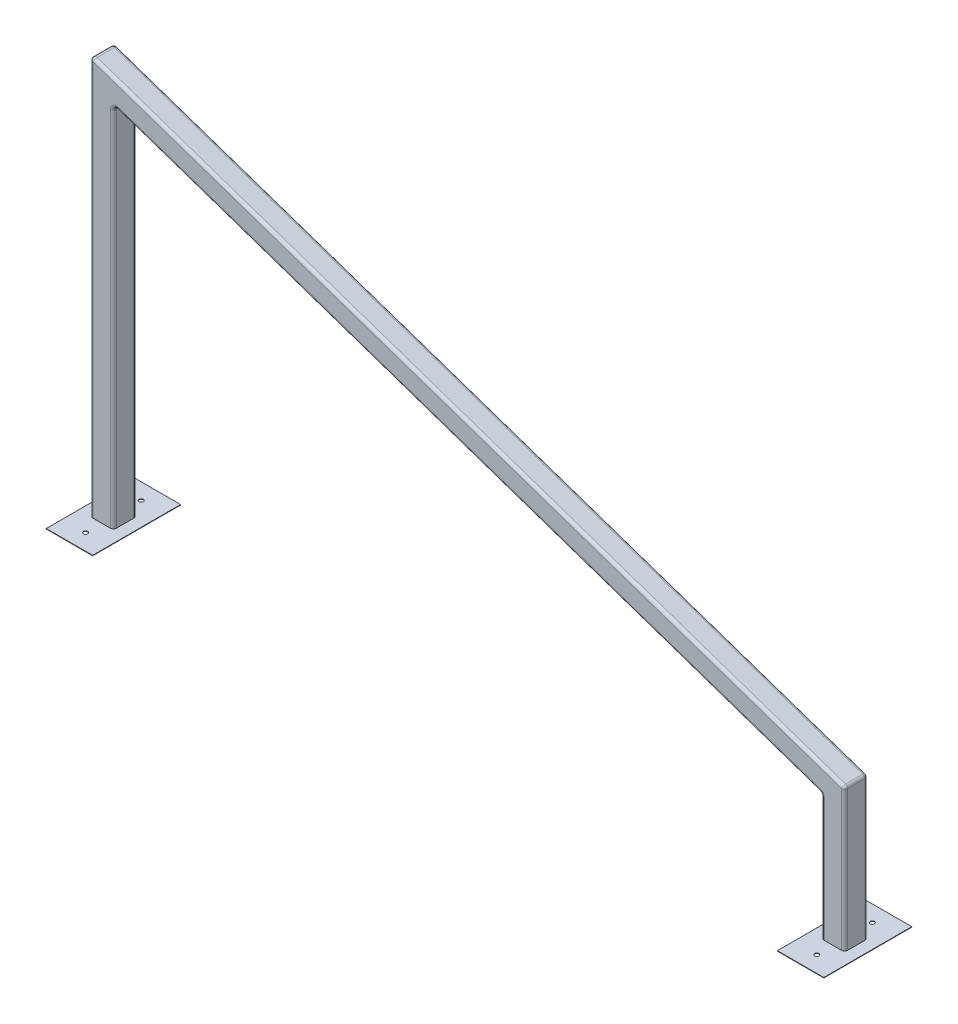
SolidWorks part; units mm, degrees
ref_plane "Alzado" through (0, 0, 0) normal (0, 0, 1) x (1, 0, 0)
ref_plane "Planta" through (0, 0, 0) normal (0, 1, 0) x (1, 0, 0)
ref_plane "Vista lateral" through (0, 0, 0) normal (1, 0, 0) x (0, 0, -1)
sketch "Croquis1" plane through (0, 0, 0) normal (0, 0, 1) x (1, 0, 0)
  line L0 (19.05, 0) -> (19.05, 600.7623)
  line L1 (19.05, 600.7623) -> (1178.0763, 205.7334)
  line L2 (1178.0763, 205.7334) -> (1178.0763, 0)
  line L3 (1178.0763, 0) -> (1216.1763, 0)
  line L4 (1216.1763, 0) -> (1216.1763, 233)
  line L5 (1216.1763, 233) -> (-19.05, 654)
  line L6 (-19.05, 654) -> (-19.05, 0)
  line L7 (-19.05, 0) -> (19.05, 0)
  point P6 (0, 0)
  point P10 (0, 0)
  dimension "D1" = 654
  dimension "D2" = 233
  dimension "D3" = 1305
  dimension "D4" = 38.1
  dimension "D5" = 38.1
extrude "Saliente-Extruir1" add sketch "Croquis1" along normal mid plane 38.1
sketch "Croquis3" plane through (0, 0, 0) normal (0, -1, 0) x (1, 0, 0)
  line L0 (1197.1263, 19.05) -> (1197.1263, 72) construction
  line L1 (38, -72) -> (-38, -72)
  line L2 (38, -72) -> (38, 72)
  line L3 (38, 72) -> (-38, 72)
  line L4 (-38, -72) -> (-38, 72)
  line L5 (38, -72) -> (-38, 72) construction
  line L6 (38, 72) -> (-38, -72) construction
  line L7 (1178.0763, 19.05) -> (1178.0763, -19.05) construction
  line L8 (1178.0763, 0) -> (1216.1763, 0) construction
  line L9 (1216.1763, 19.05) -> (1216.1763, -19.05) construction
  line L10 (0, 19.05) -> (0, 72) construction
  line L11 (1159.1263, -72) -> (1235.1263, -72)
  line L12 (1159.1263, -72) -> (1159.1263, 72)
  line L13 (1159.1263, 72) -> (1235.1263, 72)
  line L14 (1235.1263, -72) -> (1235.1263, 72)
  line L15 (1159.1263, -72) -> (1235.1263, 72) construction
  line L16 (1159.1263, 72) -> (1235.1263, -72) construction
  line L17 (-19.05, 19.05) -> (19.05, 19.05) construction
  line L18 (0, -19.05) -> (0, -72) construction
  line L19 (-19.05, -19.05) -> (19.05, -19.05) construction
  line L20 (1178.0763, 19.05) -> (1216.1763, 19.05) construction
  line L21 (1197.1263, -19.05) -> (1197.1263, -72) construction
  line L22 (1178.0763, -19.05) -> (1216.1763, -19.05) construction
  circle A0 centre (0, 45.525) radius 3.5
  circle A1 centre (0, -45.525) radius 3.5
  circle A2 centre (1197.1263, 45.525) radius 3.5
  circle A3 centre (1197.1263, -45.525) radius 3.5
  point P0 (0, 0)
  point P10 (1197.1263, 0)
  dimension "D3" = 7
  dimension "D1" = 76
  dimension "D2" = 144
extrude "Saliente-Extruir2" add sketch "Croquis3" along normal blind 0.75
fillet "Redondeo1" radius 5 16 edges at (19.05, 300.3812, 19.05) (1178.0763, 205.7334, 0) (19.05, 600.7623, 0) (-19.05, 654, 0) (1216.1763, 233, 0) (1216.1763, 116.5, 19.05) (1178.0763, 102.8667, 19.05) (1216.1763, 116.5, -19.05) (1178.0763, 102.8667, -19.05) (598.5631, 403.2479, -19.05) (598.5631, 443.5, -19.05) (598.5631, 403.2479, 19.05) (598.5631, 443.5, 19.05) (-19.05, 327, 19.05) (-19.05, 327, -19.05) (19.05, 300.3812, -19.05)
